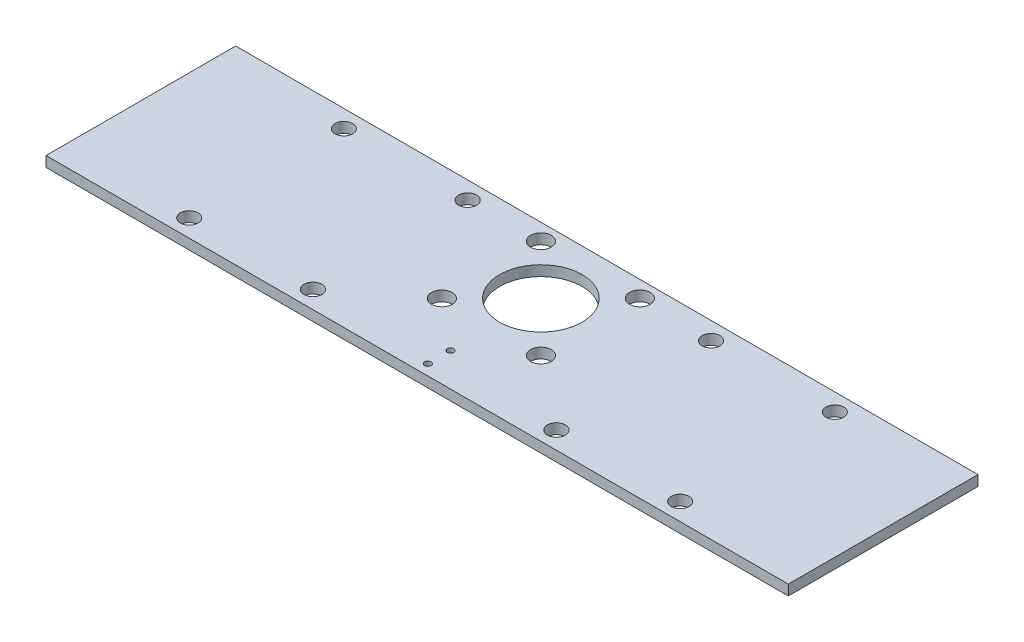
SolidWorks part; units mm, degrees
ref_plane "Front Plane" through (0, 0, 0) normal (0, 0, 1) x (1, 0, 0)
ref_plane "Top Plane" through (0, 0, 0) normal (0, 1, 0) x (1, 0, 0)
ref_plane "Right Plane" through (0, 0, 0) normal (1, 0, 0) x (0, 0, -1)
sketch "Sketch1" plane through (0, 0, 0) normal (0, 1, 0) x (1, 0, 0)
  line L1 (-228.6, 40.64) -> (228.6, 40.64)
  line L2 (-228.6, 40.64) -> (-228.6, -76.2)
  line L4 (228.6, 40.64) -> (228.6, -76.2)
  line L9 (-228.6, -76.2) -> (228.6, -76.2)
  point P0 (0, 0)
  point P10 (0, -76.2)
  dimension "D1" = 116.84
  dimension "D2" = 457.2
  dimension "D4" = 76.2
extrude "Boss-Extrude1" add sketch "Sketch1" along normal mid plane 6.35
hole_wizard "1 (1) Diameter Hole1" positions "Sketch3" profile "Sketch2" hole size "1" standard "ANSI Inch" end condition through all
sketch "Sketch3" plane through (0, 3.175, 0) normal (0, 1, 0) x (1, 0, 0)
  point P0 (0, 0)
sketch "Sketch2" plane through (0, 3.175, 0) normal (1, 0, 0) x (0, 0, 1)
  line L0 (0, 0) -> (0, 6.35)
  line L1 (0, 6.35) -> (25.4, 6.35)
  line L2 (25.4, 6.35) -> (25.4, 0)
  line L5 (25.4, 0) -> (0, 0)
  line L11 (0, -6.35) -> (0, 107.95) construction
  dimension "Thru Hole Dia." = 50.8
  dimension "Thru Hole Depth" = 6.35
hole_wizard "1/2 (0.5) Diameter Hole1" positions "Sketch5" profile "Sketch4" hole size "1/2" standard "ANSI Inch" end condition through all
sketch "Sketch5" plane through (0, 3.175, 0) normal (0, 1, 0) x (1, 0, 0)
  line L1 (-30.48, 30.48) -> (30.48, 30.48)
  line L2 (-30.48, 30.48) -> (-30.48, -30.48)
  line L3 (-30.48, -30.48) -> (30.48, -30.48)
  line L4 (30.48, 30.48) -> (30.48, -30.48)
  line L5 (-30.48, 30.48) -> (30.48, -30.48) construction
  line L6 (-30.48, -30.48) -> (30.48, 30.48) construction
  point P2 (30.48, -30.48)
  point P5 (-30.48, 30.48)
  point P6 (-30.48, -30.48)
  point P7 (30.48, 30.48)
  dimension "D1" = 60.96
sketch "Sketch4" plane through (30.48, 3.175, 30.48) normal (1, 0, 0) x (0, 0, 1)
  line L0 (0, 0) -> (0, 6.35)
  line L1 (0, 6.35) -> (6.35, 6.35)
  line L2 (6.35, 6.35) -> (6.35, 0)
  line L5 (6.35, 0) -> (0, 0)
  line L11 (0, -6.35) -> (0, 107.95) construction
  dimension "Thru Hole Dia." = 12.7
  dimension "Thru Hole Depth" = 6.35
hole_wizard "Ø4.0 (4) Diameter Hole1" positions "Sketch7" profile "Sketch6" hole size "Ø4.0" standard "ANSI Metric" end condition through all
sketch "Sketch7" plane through (0, 3.175, 0) normal (0, 1, 0) x (1, 0, 0)
  point P0 (0, -55.63)
  point P2 (0, -69.63)
  dimension "D1" = 55.63
  dimension "D2" = 14
sketch "Sketch6" plane through (0, 3.175, 55.63) normal (1, 0, 0) x (0, 0, 1)
  line L0 (0, 0) -> (0, 6.35)
  line L1 (0, 6.35) -> (2, 6.35)
  line L2 (2, 6.35) -> (2, 0)
  line L5 (2, 0) -> (0, 0)
  line L11 (0, -6.35) -> (0, 107.95) construction
  dimension "Thru Hole Dia." = 4
  dimension "Thru Hole Depth" = 6.35
hole_wizard "M10 Clearance Hole1" positions "Sketch9" profile "Sketch8" hole size "M10" standard "ANSI Metric" end condition through all
sketch "Sketch9" plane through (0, 3.175, 0) normal (0, 1, 0) x (1, 0, 0)
  line L1 (-75, 29.845) -> (75, 29.845)
  line L2 (-75, 29.845) -> (-75, -65.405)
  line L3 (-75, -65.405) -> (75, -65.405)
  line L4 (75, 29.845) -> (75, -65.405)
  line L5 (228.6, -17.78) -> (-228.6, -17.78) construction
  line L6 (228.6, -76.2) -> (228.6, 40.64) construction
  line L7 (-228.6, 40.64) -> (-228.6, -76.2) construction
  point P2 (75, -65.405)
  point P5 (-75, 29.845)
  point P6 (-75, -65.405)
  point P7 (75, 29.845)
  point P17 (75, -17.78)
  point P18 (0, 29.845)
  dimension "D1" = 95.25
  dimension "D2" = 150
sketch "Sketch8" plane through (75, 3.175, 65.405) normal (1, 0, 0) x (0, 0, 1)
  line L0 (0, 0) -> (0, 6.35)
  line L1 (0, 6.35) -> (5.5, 6.35)
  line L2 (5.5, 6.35) -> (5.5, 0)
  line L5 (5.5, 0) -> (0, 0)
  line L11 (0, -6.35) -> (0, 107.95) construction
  dimension "Thru Hole Dia." = 11
  dimension "Thru Hole Depth" = 6.35
sketch "Sketch11" plane through (0, 3.175, 0) normal (0, 1, 0) x (1, 0, 0)
  line L6 (-75, 29.845) -> (-151.2, 29.845) construction
  line L7 (-75, 29.845) -> (-75, -65.405) construction
  line L8 (-75, -65.405) -> (-151.2, -65.405) construction
  line L9 (-151.2, 29.845) -> (-151.2, -65.405) construction
  line L10 (75, -65.405) -> (151.2, -65.405) construction
  line L11 (75, -65.405) -> (75, 29.845) construction
  line L12 (75, 29.845) -> (151.2, 29.845) construction
  line L13 (151.2, -65.405) -> (151.2, 29.845) construction
  circle A0 centre (-151.2, 29.845) radius 5.461
  circle A1 centre (-151.2, -65.405) radius 5.461
  circle A2 centre (151.2, 29.845) radius 5.461
  circle A3 centre (151.2, -65.405) radius 5.461
  dimension "D2" = 10.922
  dimension "D1" = 76.2
extrude "Aux Clearance holes" cut sketch "Sketch11" against normal up to next
